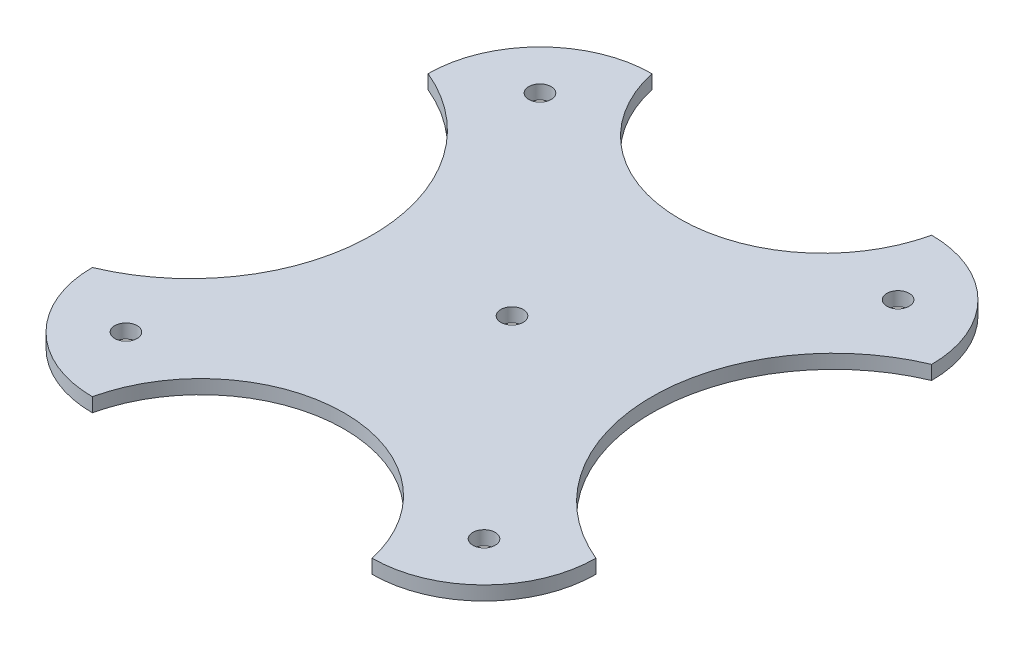
SolidWorks part; units mm, degrees
ref_plane "Piano frontale" through (0, 0, 0) normal (0, 0, 1) x (1, 0, 0)
ref_plane "Piano superiore" through (0, 0, 0) normal (0, 1, 0) x (1, 0, 0)
ref_plane "Piano destro" through (0, 0, 0) normal (1, 0, 0) x (0, 0, -1)
sketch "Schizzo1" plane through (0, 0, 0) normal (0, 1, 0) x (1, 0, 0)
  line L0 (-27.0711, 40.2596) -> (12.9289, 40.2596) construction
  line L1 (-27.0711, 40.2596) -> (152.9289, 40.2596) construction
  line L2 (-27.0711, 40.2596) -> (-27.0711, -159.7404) construction
  line L3 (-27.0711, -159.7404) -> (152.9289, -159.7404) construction
  line L4 (152.9289, 40.2596) -> (152.9289, -159.7404) construction
  line L5 (152.9289, 40.2596) -> (112.9289, 40.2596) construction
  line L6 (-27.0711, 40.2596) -> (-27.0711, 0.2596) construction
  line L7 (152.9289, 40.2596) -> (152.9289, 0.2596) construction
  line L8 (-27.0711, -159.7404) -> (-27.0711, -119.7404) construction
  line L9 (-27.0711, -159.7404) -> (12.9289, -159.7404) construction
  line L10 (152.9289, -159.7404) -> (112.9289, -159.7404) construction
  line L11 (152.9289, -159.7404) -> (152.9289, -119.7404) construction
  line L12 (12.9289, 40.2596) -> (12.9289, -159.7404) construction
  line L13 (-27.0711, -119.7404) -> (152.9289, -119.7404) construction
  line L14 (-27.0711, 0.2596) -> (152.9289, 0.2596) construction
  line L15 (112.9289, 40.2596) -> (112.9289, -159.7404) construction
  line L16 (-27.0711, 40.2596) -> (152.9289, -159.7404) construction
  line L17 (-27.0711, -159.7404) -> (152.9289, 40.2596) construction
  arc A0 (12.9289, 40.2596) -> (-27.0711, 0.2596) centre (12.9289, 0.2596) ccw
  arc A1 (112.9289, 40.2596) -> (152.9289, 0.2596) centre (112.9289, 0.2596) cw
  arc A2 (152.9289, -119.7404) -> (112.9289, -159.7404) centre (112.9289, -119.7404) cw
  arc A3 (12.9289, -159.7404) -> (-27.0711, -119.7404) centre (12.9289, -119.7404) cw
  arc A4 (-27.0711, 0.2596) -> (-27.0711, -119.7404) centre (-52.0711, -59.7404) cw
  arc A5 (152.9289, 0.2596) -> (152.9289, -119.7404) centre (177.9289, -59.7404) ccw
  arc A6 (112.9289, -159.7404) -> (12.9289, -159.7404) centre (62.9289, -170.9904) ccw
  arc A7 (112.9289, 40.2596) -> (12.9289, 40.2596) centre (62.9289, 51.5096) cw
  circle A8 centre (-1.0711, 14.2596) radius 4
  circle A9 centre (126.9289, 14.2596) radius 4
  circle A10 centre (126.9289, -133.7404) radius 4
  circle A11 centre (-1.0711, -133.7404) radius 4
  circle A12 centre (62.9289, -59.7404) radius 4
  dimension "D4" = 8
  dimension "D5" = 14
  dimension "D6" = 14
  dimension "D7" = 14
  dimension "D8" = 14
  dimension "D9" = 14
  dimension "D10" = 14
  dimension "D11" = 14
  dimension "D12" = 14
  dimension "D13" = 8
  dimension "D1" = 180
  dimension "D2" = 200
  dimension "D3" = 40
extrude "Estrusione-Estrusione1" add sketch "Schizzo1" along normal blind 5
